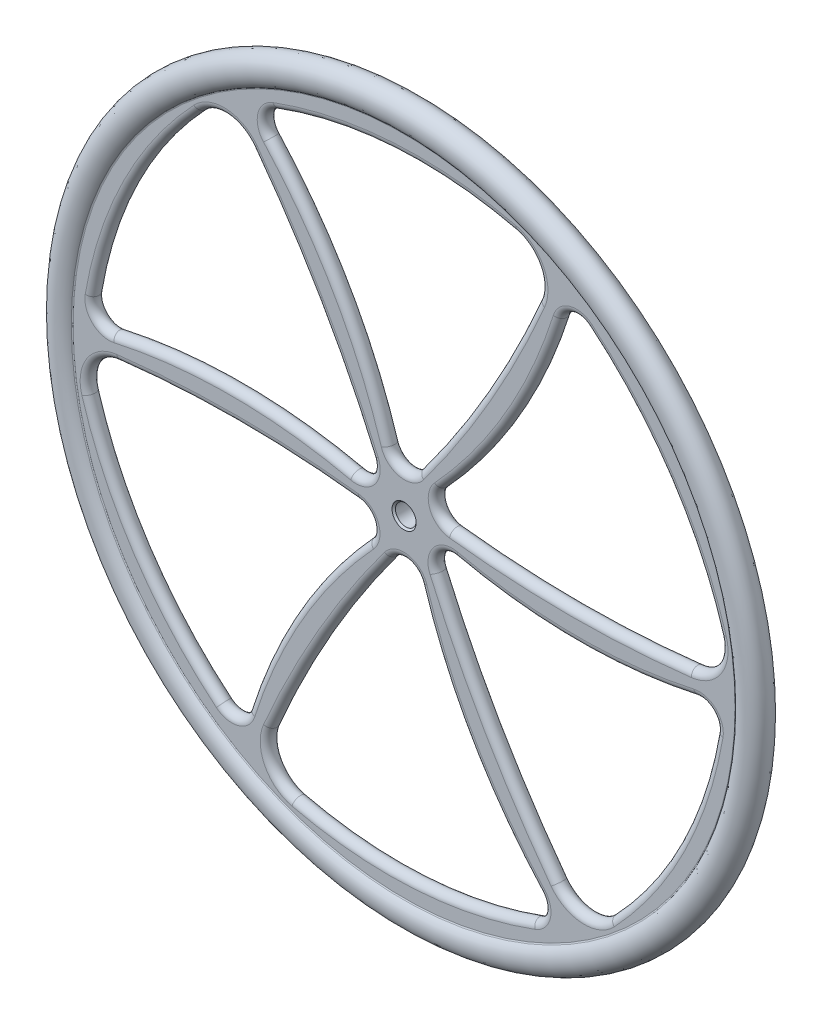
SolidWorks part; units mm, degrees
ref_plane "Front Plane" through (0, 0, 0) normal (0, 0, 1) x (1, 0, 0)
ref_plane "Top Plane" through (0, 0, 0) normal (0, 1, 0) x (1, 0, 0)
ref_plane "Right Plane" through (0, 0, 0) normal (1, 0, 0) x (0, 0, -1)
sketch "Sketch1" plane through (0, 0, 0) normal (0, 1, 0) x (1, 0, 0)
  line L0 (1.5, 0) -> (1.5, 3)
  line L1 (0, 0) -> (50, 0) construction
  line L2 (0, 0) -> (0, 2) construction
  line L3 (0, 2) -> (50, 2) construction
  line L4 (50, 0) -> (50, 2) construction
  line L5 (1.5, 3) -> (2, 3)
  line L6 (2, 3) -> (2, 2)
  line L7 (2, 2) -> (48.1281, 2)
  line L8 (48.1281, 0) -> (1.5, 0)
  ellipse E0 centre (50, 1) end of major axis (47.775, 1) minor radius 1.85
  dimension "D1" = 50
  dimension "D2" = 2
  dimension "D3" = 4.45
  dimension "D4" = 3.7
  dimension "D5" = 1.5
  dimension "D6" = 0.5
  dimension "D7" = 1
revolve "Revolve1" add sketch "Sketch1" angle 360 about L2 region at (24.5715, 0, -1.008) region at (50, 0, -1)
sketch "Sketch2" plane through (0, 0, 0) normal (0, 0, 1) x (1, 0, 0)
  line L0 (48.1281, 0) -> (0, 0) construction
  line L1 (0, 0) -> (24.064, 41.6801) construction
  circle A0 centre (0, 0) radius 48.1281 construction
  circle A1 centre (7, 4) radius 2.5 construction
  circle A2 centre (41, 6.5) radius 5 construction
  circle A3 centre (25, 35) radius 2.5 construction
  arc A4 (6.7106, 1.5168) -> (41.5837, 1.5342) centre (24.0729, 150.5086) ccw
  arc A5 (45.79, 7.9339) -> (26.5952, 36.9249) centre (-11.6897, -9.2732) ccw
  arc A6 (22.6169, 35.7557) -> (5.1624, 5.6951) centre (-53.641, 59.9367) cw
  arc A7 (41.5837, 1.5342) -> (45.79, 7.9339) centre (41, 6.5) ccw
  arc A8 (26.5952, 36.9249) -> (22.6169, 35.7557) centre (25, 35) ccw
  arc A9 (5.1624, 5.6951) -> (6.7106, 1.5168) centre (7, 4) ccw
  dimension "D3" = 5
  dimension "D5" = 5
  dimension "D8" = 10
  dimension "D11" = 80
  dimension "D12" = 60
  dimension "D13" = 150
  dimension "D1" = 60
  dimension "D2" = 4
  dimension "D4" = 7
  dimension "D6" = 25
  dimension "D7" = 35
  dimension "D9" = 6.5
  dimension "D10" = 41
extrude "Cut-Extrude1" cut sketch "Sketch2" against normal through all
fillet "Fillet1" 12 edges at (24.1477, 0.5086, 0) (4.6558, 3.1314, 0) (15.5421, 19.7659, 0) (24.295, 37.3985, 0) (38.3386, 23.8503, 0) (45.1783, 3.7538, 0) (15.5421, 19.7659, -2) (4.6558, 3.1314, -2) (24.1477, 0.5086, -2) (45.1783, 3.7538, -2) (38.3386, 23.8503, -2) (24.295, 37.3985, -2) type full round first side face at (25.3596, 14.7347, 0) second side face at (25.3596, 14.7347, -2) middle face at (24.4506, 36.8694, -1) middle face at (37.2656, 23.1399, -1) middle face at (44.4326, 4.2439, -1) middle face at (14.7159, 20.2456, -1) middle face at (5.2961, 3.3686, -1) middle face at (24.1474, 1.0171, -1)
fillet "Fillet2" radius 0.25 1 edges at (48.1281, 0, 0)
chamfer "Chamfer1" distance 0.25 angle 45 2 edges at (1.5, 0, 0) (1.5, 0, -3)
pattern_circular "CirPattern2" count 6 over 360 of "Fillet1", "Cut-Extrude1"
